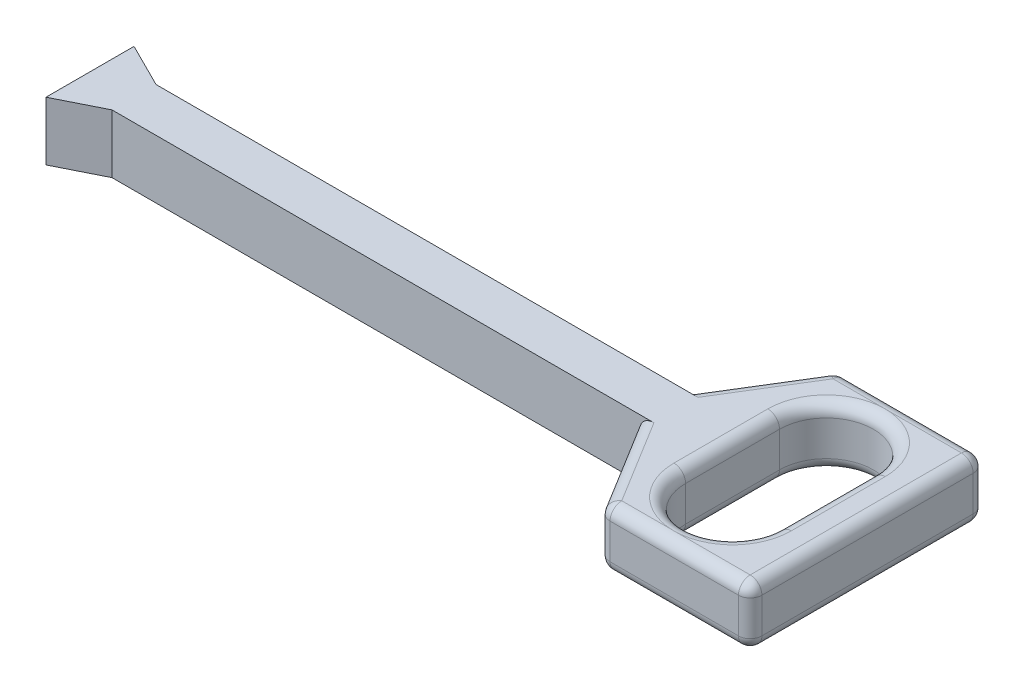
SolidWorks part; units mm, degrees
ref_plane "Front Plane" through (0, 0, 0) normal (0, 0, 1) x (1, 0, 0)
ref_plane "Top Plane" through (0, 0, 0) normal (0, 1, 0) x (1, 0, 0)
ref_plane "Right Plane" through (0, 0, 0) normal (1, 0, 0) x (0, 0, -1)
sketch "Sketch1" plane through (0, 0, 0) normal (0, 1, 0) x (1, 0, 0)
  line L0 (0, 0) -> (0, -7.5)
  line L1 (0, -7.5) -> (7.5, -3.75)
  line L2 (117.5, 8) -> (117.5, -8) construction
  line L3 (7.5, -3.75) -> (97.5, -3.75)
  line L4 (97.5, -3.75) -> (107.5, -20)
  line L5 (107.5, -20) -> (132.5, -20)
  line L6 (132.5, -20) -> (132.5, 20)
  line L7 (132.5, 20) -> (107.5, 20)
  line L8 (107.5, 20) -> (97.5, 3.75)
  line L9 (97.5, 3.75) -> (7.5, 3.75)
  line L10 (125.5, 8) -> (125.5, -8)
  line L11 (7.5, 3.75) -> (0, 7.5)
  line L12 (0, 7.5) -> (0, 0)
  line L13 (109.5, 8) -> (109.5, -8)
  arc A0 (125.5, 8) -> (109.5, 8) centre (117.5, 8) ccw
  arc A1 (109.5, -8) -> (125.5, -8) centre (117.5, -8) ccw
  point P5 (117.5, 0)
  dimension "D1" = 15
  dimension "D2" = 7.5
  dimension "D3" = 7.5
  dimension "D4" = 90
  dimension "D5" = 7.5
  dimension "D6" = 40
  dimension "D7" = 25
  dimension "D8" = 10
  dimension "D9" = 16
  dimension "D10" = 16
  dimension "D11" = 7
extrude "Boss-Extrude1" add sketch "Sketch1" along normal blind 10
fillet "Fillet1" radius 2 8 edges at (117.5, 0, -16) (125.5, 0, 0) (117.5, 0, 16) (117.5, 10, 16) (109.5, 10, 0) (117.5, 10, -16) (109.5, 0, 0) (125.5, 10, 0)
fillet "Fillet2" radius 2 14 edges at (102.5, 0, 11.875) (102.5, 10, 11.875) (107.5, 5, 20) (132.5, 5, 20) (132.5, 5, -20) (107.5, 5, -20) (102.5, 10, -11.875) (102.5, 0, -11.875) (120, 0, -20) (120, 10, -20) (120, 0, 20) (120, 10, 20) (132.5, 0, 0) (132.5, 10, 0)
sketch "Sketch3" plane through (0, 0, 0) normal (0, -1, 0) x (1, 0, 0)
  line L0 (7.5, 3.75) -> (0, 7.5)
  line L1 (0, 7.5) -> (0, -7.5)
  line L2 (0, -7.5) -> (7.5, -3.75)
  line L3 (7.5, -3.75) -> (7.5, 3.75)
